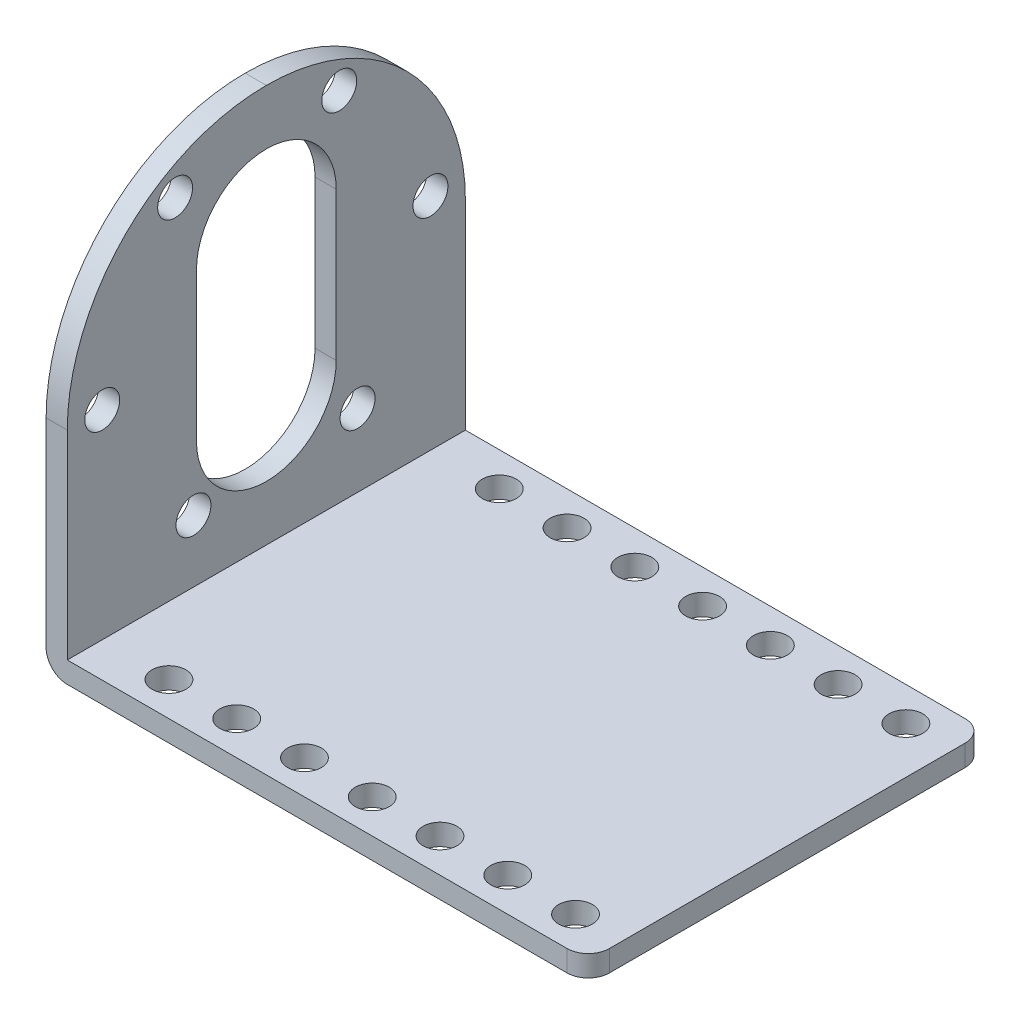
SolidWorks part; units mm, degrees
material "1060 Alloy"
ref_plane "Front Plane" through (0, 0, 0) normal (0, 0, 1) x (1, 0, 0)
ref_plane "Top Plane" through (0, 0, 0) normal (0, 1, 0) x (1, 0, 0)
ref_plane "Right Plane" through (0, 0, 0) normal (1, 0, 0) x (0, 0, -1)
sketch "Sketch1" plane through (0, 0, 0) normal (0, 1, 0) x (1, 0, 0)
  line L1 (-25.6, 18.8) -> (25.6, 18.8)
  line L2 (-25.6, 18.8) -> (-25.6, -18.8)
  line L3 (-25.6, -18.8) -> (25.6, -18.8)
  line L4 (25.6, 18.8) -> (25.6, -18.8)
  line L5 (-25.6, 18.8) -> (25.6, -18.8) construction
  line L6 (-25.6, -18.8) -> (25.6, 18.8) construction
  point P0 (0, 0)
  dimension "D1" = 51.2
  dimension "D2" = 37.6
extrude "Boss-Extrude1" add sketch "Sketch1" along normal blind 2
sketch "Sketch2" plane through (0, 2, 0) normal (0, 1, 0) x (1, 0, 0)
  line L0 (-25.6, -18.8) -> (25.6, -18.8) construction
  line L1 (-25.6, 18.8) -> (-23.6, 18.8)
  line L2 (-25.6, 18.8) -> (-25.6, -18.8)
  line L3 (-25.6, -18.8) -> (-23.6, -18.8)
  line L4 (-23.6, 18.8) -> (-23.6, -18.8)
  dimension "D1" = 2
extrude "Boss-Extrude2" add sketch "Sketch2" along normal blind 37.6
sketch "Sketch3" plane through (-25.6, 0, 0) normal (-1, 0, 0) x (0, 0, 1)
  line L0 (0, 0) -> (0, 39.6) construction
  line L1 (-18.8, 39.6) -> (18.8, 39.6) construction
  line L2 (-18.8, 0) -> (18.8, 0) construction
  line L3 (0, 20.8) -> (15.5, 20.8) construction
  circle A0 centre (0, 20.8) radius 15.5 construction
  circle A1 centre (15.5, 20.8) radius 1.65
  circle A2 centre (6.884, 7.8766) radius 1.65
  circle A3 centre (-8.616, 8.8766) radius 1.65
  circle A4 centre (-15.5, 22.8) radius 1.65
  circle A5 centre (-6.884, 35.7234) radius 1.65
  circle A6 centre (8.616, 34.7234) radius 1.65
  point P24 (0, 21.8)
  dimension "D1" = 31
  dimension "D3" = 3.3
  dimension "D2" = 20.8
  dimension "D4" = 6
extrude "Cut-Extrude2" cut sketch "Sketch3" against normal blind 37.6
sketch "Sketch5" plane through (-25.6, 0, 0) normal (-1, 0, 0) x (0, 0, 1)
  line L0 (0, 39.6) -> (0, 0.3488) construction
  line L1 (-18.8, 39.6) -> (18.8, 39.6) construction
  line L2 (18.8, 20.8) -> (-18.8, 20.8) construction
  line L3 (18.8, 39.6) -> (18.8, 0) construction
  line L4 (-18.8, 39.6) -> (-18.8, 0) construction
  line L5 (-18.8, 0) -> (18.8, 0) construction
  line L6 (6.6, 27.8) -> (6.6, 13.8)
  line L7 (-6.6, 27.8) -> (-6.6, 13.8)
  circle A0 centre (0, 27.8) radius 6.6
  circle A1 centre (0, 13.8) radius 6.6
  dimension "D2" = 13.2
  dimension "D3" = 13.2
  dimension "D1" = 20.8
  dimension "D4" = 7
  dimension "D5" = 7
extrude "Cut-Extrude3" cut sketch "Sketch5" against normal blind 37.6 contours A0 | A1 L6 A0 L7 | A1 region at (-25.6, 27.8, 0) region at (-25.6, 20.8, 0) region at (-25.6, 13.8, 0)
sketch "Sketch6" plane through (0, 0, 0) normal (0, -1, 0) x (-1, 0, 0)
  line L0 (25.6, -15.6) -> (-25.4417, -15.6) construction
  line L1 (25.6, 18.8) -> (25.6, -18.8) construction
  line L2 (25.6, 0) -> (-25.6, 0) construction
  line L3 (-25.6, -18.8) -> (-25.6, 18.8) construction
  circle A0 centre (17.2, -15.6) radius 1.6
  circle A1 centre (10.8, -15.6) radius 1.6
  circle A2 centre (4.4, -15.6) radius 1.6
  circle A3 centre (-2, -15.6) radius 1.6
  circle A4 centre (-8.4, -15.6) radius 1.6
  circle A5 centre (-14.8, -15.6) radius 1.6
  circle A6 centre (-21.2, -15.6) radius 1.6
  circle A7 centre (-21.2, 15.6) radius 1.6
  circle A8 centre (-14.8, 15.6) radius 1.6
  circle A9 centre (-8.4, 15.6) radius 1.6
  circle A10 centre (-2, 15.6) radius 1.6
  circle A11 centre (4.4, 15.6) radius 1.6
  circle A12 centre (10.8, 15.6) radius 1.6
  circle A13 centre (17.2, 15.6) radius 1.6
  dimension "D2" = 3.2
  dimension "D1" = 15.6
  dimension "D3" = 8.4
  dimension "D4" = 7
extrude "Cut-Extrude4" cut sketch "Sketch6" against normal blind 37.6
fillet "Fillet1" radius 2 2 edges at (25.6, 1, -18.8) (25.6, 1, 18.8)
fillet "Fillet2" radius 2 1 edges at (-25.6, 0, 0)
fillet "Fillet3" radius 18.8 2 edges at (-24.6, 39.6, -18.8) (-24.6, 39.6, 18.8)
